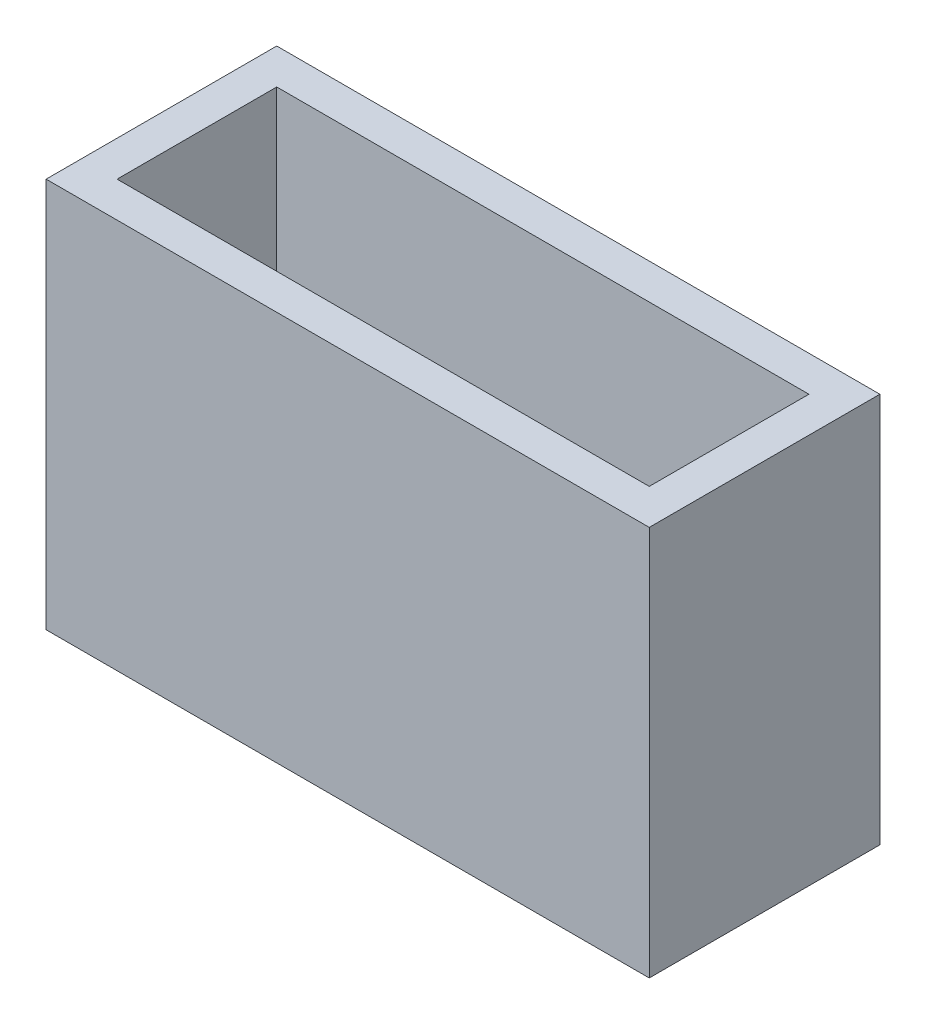
SolidWorks part; units mm, degrees
ref_plane "Front Plane" through (0, 0, 0) normal (0, 0, 1) x (1, 0, 0)
ref_plane "Top Plane" through (0, 0, 0) normal (0, 1, 0) x (1, 0, 0)
ref_plane "Right Plane" through (0, 0, 0) normal (1, 0, 0) x (0, 0, -1)
sketch "Sketch1" plane through (0, 0, 0) normal (0, 1, 0) x (1, 0, 0)
  line L1 (-170, -65) -> (170, -65)
  line L2 (-170, -65) -> (-170, 65)
  line L3 (-170, 65) -> (170, 65)
  line L4 (170, -65) -> (170, 65)
  line L5 (-170, -65) -> (170, 65) construction
  line L6 (-170, 65) -> (170, -65) construction
  line L10 (-150, 45) -> (150, 45)
  line L11 (150, -45) -> (150, 45)
  line L12 (-150, -45) -> (150, -45)
  line L13 (-150, -45) -> (-150, 45)
  point P0 (0, 0)
  dimension "D1" = 340
  dimension "D2" = 130
  dimension "D3" = 20
extrude "Boss-Extrude1" add sketch "Sketch1" along normal blind 220
extrude "Boss-Extrude2" add sketch "Sketch1<2>" along normal blind 220
sketch "Sketch1<2>" plane through (0, 0, 0) normal (0, 1, 0) x (1, 0, 0) same geometry as "Sketch1"
sketch "Sketch2" plane through (-170, 0, 0) normal (-1, 0, 0) x (0, 0, 1)
  line L0 (65, 220) -> (65, 0) construction
  line L1 (-65, 0) -> (65, 0)
  line L2 (-65, 0) -> (-65, 11.669)
  line L3 (-65, 11.669) -> (65, 11.669)
  line L4 (65, 0) -> (65, 11.669)
extrude "Boss-Extrude3" add sketch "Sketch2" against normal through all
